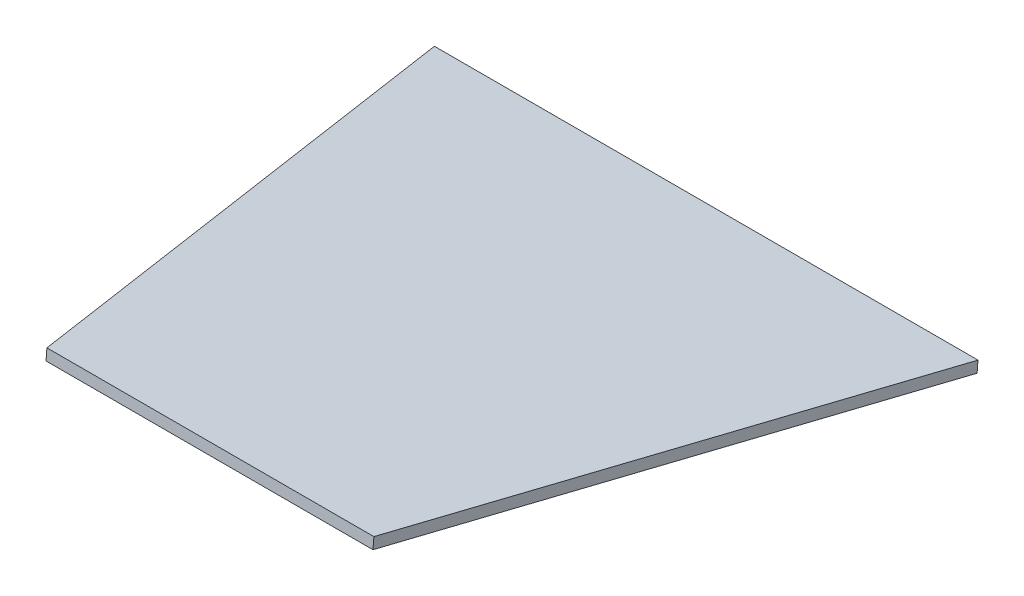
SolidWorks part; units mm, degrees
ref_plane "Front Plane" through (0, 0, 0) normal (0, 0, 1) x (1, 0, 0)
ref_plane "Top Plane" through (0, 0, 0) normal (0, 1, 0) x (1, 0, 0)
ref_plane "Right Plane" through (0, 0, 0) normal (1, 0, 0) x (0, 0, -1)
ref_plane "Plane1" through (-0.0001, -1762.2845, 145.377) normal (0, -0.9966, 0.0822) x (-1, 0, 0)
sketch "Sketch1" plane through (-0.0001, -1762.2845, 145.377) normal (0, -0.9966, 0.0822) x (-1, 0, 0)
  line L0 (927.9324, -1893.2884) -> (1306.8393, -1893.2884)
  line L1 (1306.8393, -1893.2884) -> (1432.3521, -1316.7398)
  line L2 (1432.3521, -1316.7398) -> (802.4196, -1316.7398)
  line L3 (802.4196, -1316.7398) -> (927.9324, -1893.2884)
  line L4 (802.4183, -1316.7398) -> (1432.3534, -1316.7398) construction
  line L5 (928.076, -1893.948) -> (801.0629, -1310.5075) construction
  line L6 (1433.7088, -1310.5075) -> (1306.6957, -1893.948) construction
  line L7 (1306.8419, -1893.2884) -> (927.9298, -1893.2884) construction
extrude "Boss-Extrude1" add sketch "Sketch1" along normal blind 12.7
